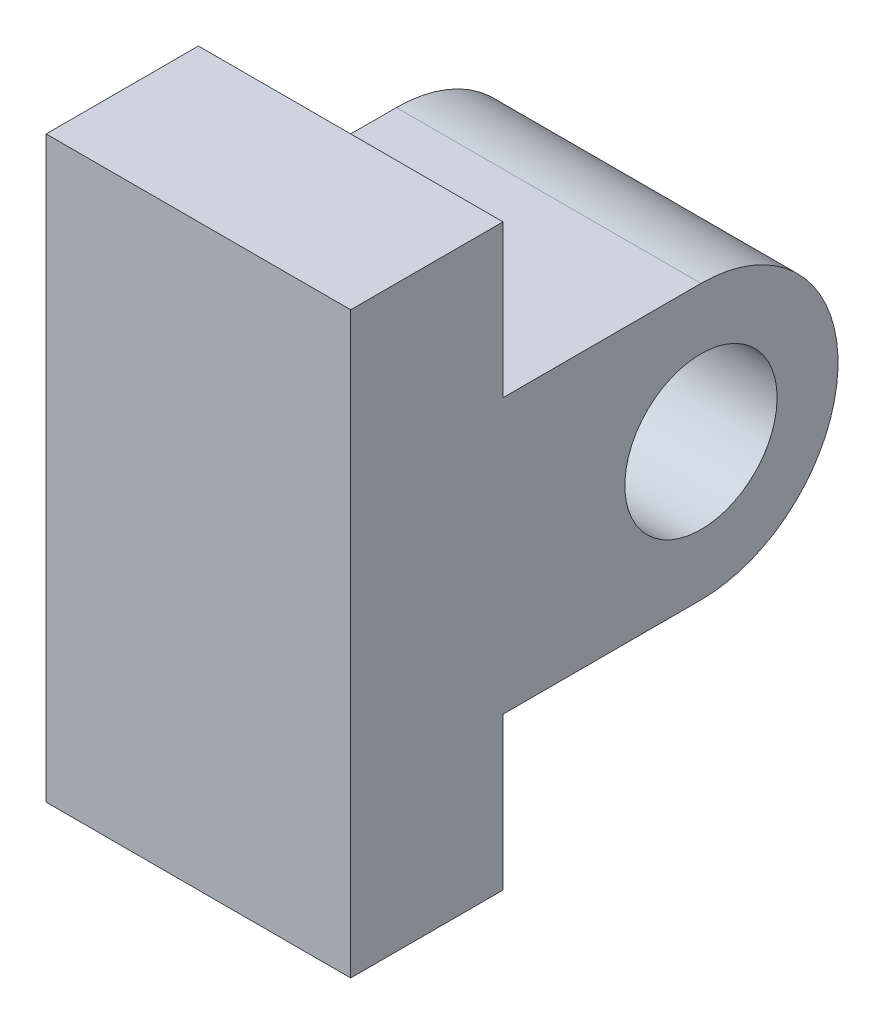
SolidWorks part; units mm, degrees
ref_plane "Front Plane" through (0, 0, 0) normal (0, 0, 1) x (1, 0, 0)
ref_plane "Top Plane" through (0, 0, 0) normal (0, 1, 0) x (1, 0, 0)
ref_plane "Right Plane" through (0, 0, 0) normal (1, 0, 0) x (0, 0, -1)
sketch "Sketch2" plane through (0, 0, 0) normal (1, 0, 0) x (0, 0, -1)
  line L0 (9, 4.5) -> (2.5, 4.5)
  line L1 (-2.5, 9.5) -> (2.5, 9.5)
  line L2 (-2.5, 9.5) -> (-2.5, -9.5)
  line L3 (-2.5, -9.5) -> (2.5, -9.5)
  line L4 (2.5, 9.5) -> (2.5, -9.5)
  line L5 (-2.5, 9.5) -> (2.5, -9.5) construction
  line L6 (-2.5, -9.5) -> (2.5, 9.5) construction
  line L7 (9, -4.5) -> (2.5, -4.5)
  line L8 (4.5, 0) -> (2.5, 0) construction
  circle A0 centre (9, 0) radius 4.5
  circle A1 centre (9, 0) radius 2.5
  point P0 (0, 0)
  point P12 (0, 0)
  point P13 (0, 0)
  dimension "D1" = 2
  dimension "D2" = 5
  dimension "D3" = 5
  dimension "D4" = 5
  dimension "D5" = 2
extrude "Boss-Extrude1" add sketch "Sketch2" along normal mid plane 10 contours L4 L1 L2 L3 | A0 L0 L4 L7 | A0 A1 region at (0, 0, -4.1529) region at (0, 3.092, -12.092) region at (0, 0, 0)
